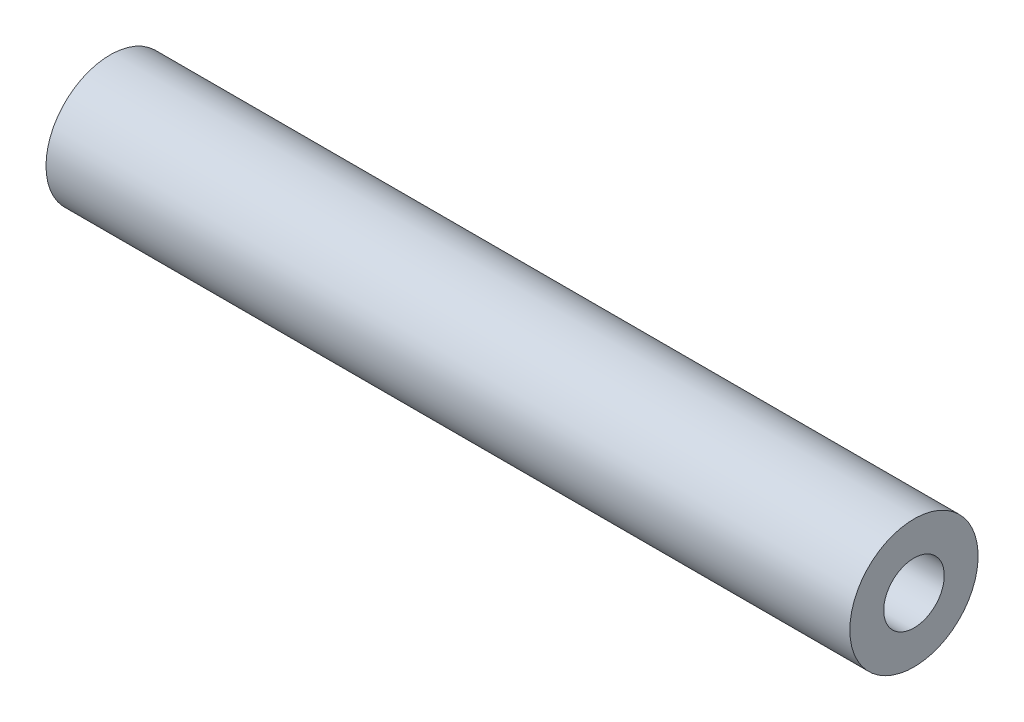
SolidWorks part; units mm, degrees
ref_plane "Front Plane" through (0, 0, 0) normal (0, 0, 1) x (1, 0, 0)
ref_plane "Top Plane" through (0, 0, 0) normal (0, 1, 0) x (1, 0, 0)
ref_plane "Right Plane" through (0, 0, 0) normal (1, 0, 0) x (0, 0, -1)
sketch "Sketch1" plane through (0, 0, 0) normal (1, 0, 0) x (0, 0, -1)
  circle A0 centre (0, 0) radius 4.7625
  dimension "D1" = 9.525
extrude "Boss-Extrude1" add sketch "Sketch1" along normal blind 59.69
hole_wizard "#12-24 Tapped Hole1" positions "Sketch3" profile "Sketch2" tap size "#12-24" standard "ANSI Inch" end condition through all
sketch "Sketch3" plane through (59.69, 0, 0) normal (1, 0, 0) x (0, 0, -1)
  point P0 (0, 0)
sketch "Sketch2" plane through (59.69, 0, 0) normal (0, 1, 0) x (0, 0, -1)
  line L0 (0, 0) -> (0, 59.69)
  line L1 (0, 59.69) -> (2.2479, 59.69)
  line L2 (2.2479, 59.69) -> (2.2479, 0)
  line L5 (2.2479, 0) -> (0, 0)
  line L11 (0, -6.35) -> (0, 107.95) construction
  dimension "Thread Major Dia." = 4.4958
  dimension "Thru Tap Drill Depth" = 59.69
